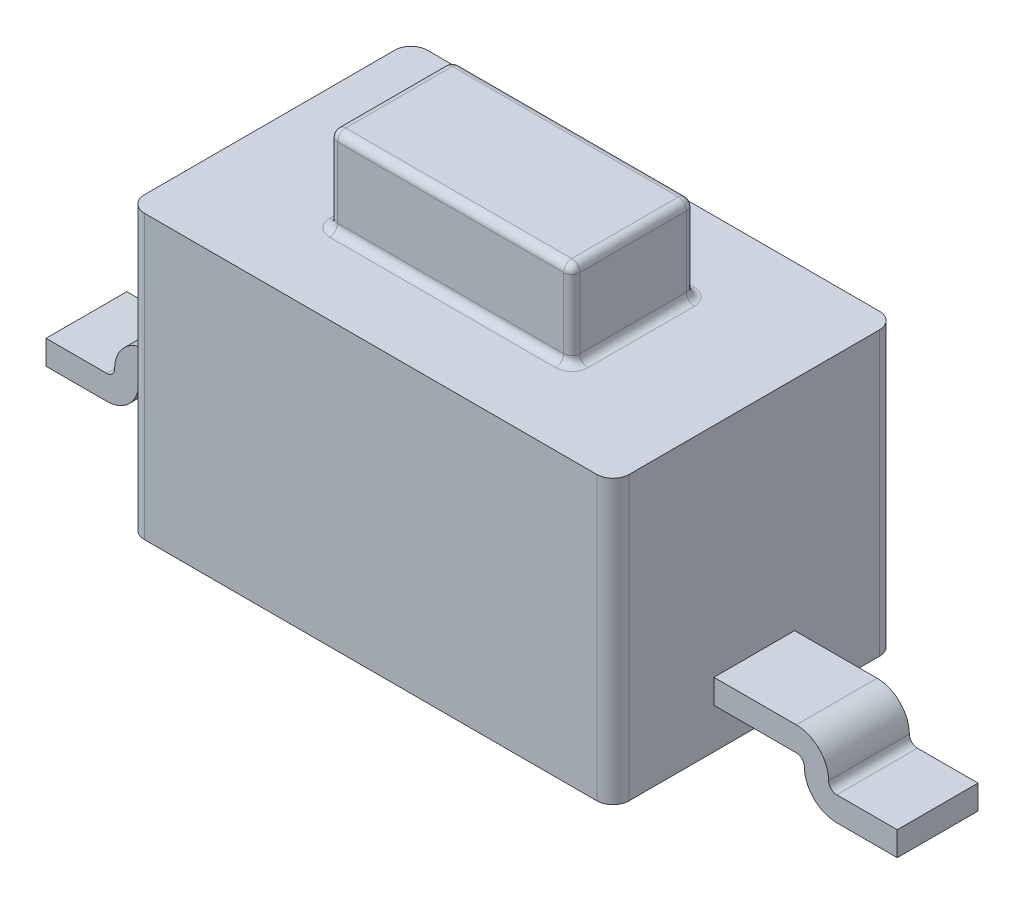
SolidWorks part; units mm, degrees
ref_plane "Front Plane" through (0, 0, 0) normal (0, 0, 1) x (1, 0, 0)
ref_plane "Top Plane" through (0, 0, 0) normal (0, 1, 0) x (1, 0, 0)
ref_plane "Right Plane" through (0, 0, 0) normal (1, 0, 0) x (0, 0, -1)
sketch "Sketch1" plane through (0, 0, 0) normal (0, 1, 0) x (1, 0, 0)
  line L0 (0, 4.6661) -> (0, -3.6864) construction
  line L1 (-7.6307, 0) -> (8.9196, 0) construction
  line L3 (-3, 1.75) -> (3, 1.75)
  line L4 (-3, 1.75) -> (-3, -1.75)
  line L5 (-3, -1.75) -> (3, -1.75)
  line L6 (3, 1.75) -> (3, -1.75)
  dimension "D1" = 3.5
  dimension "D2" = 6
  dimension "D3" = 3
  dimension "D4" = 1.75
extrude "Boss-Extrude1" add sketch "Sketch1" along normal blind 3.5
fillet "Fillet1" radius 0.2 4 edges at (-3, 1.75, -1.75) (3, 1.75, -1.75) (3, 1.75, 1.75) (-3, 1.75, 1.75)
sketch "Sketch2" plane through (0, 3.5, 0) normal (0, 1, 0) x (1, 0, 0)
  line L0 (0, 1.6315) -> (0, -1.6435) construction
  line L1 (-2.8003, 0) -> (2.578, 0) construction
  line L3 (-1.5, -0.76) -> (1.5, -0.76)
  line L4 (-1.5, -0.76) -> (-1.5, 0.76)
  line L5 (-1.5, 0.76) -> (1.5, 0.76)
  line L6 (1.5, -0.76) -> (1.5, 0.76)
  line L7 (-1.5, -0.76) -> (1.5, 0.76) construction
  line L8 (-1.5, 0.76) -> (1.5, -0.76) construction
  point P5 (0, 0)
  dimension "D1" = 3
  dimension "D2" = 1.52
extrude "Boss-Extrude2" add sketch "Sketch2" along normal blind 1.07
fillet "Fillet2" radius 0.1 12 edges at (1.5, 3.5, 0) (1.5, 4.035, -0.76) (0, 3.5, -0.76) (-1.5, 4.035, -0.76) (-1.5, 3.5, 0) (-1.5, 4.035, 0.76) (1.5, 4.035, 0.76) (0, 3.5, 0.76) (0, 4.57, 0.76) (-1.5, 4.57, 0) (0, 4.57, -0.76) (1.5, 4.57, 0)
sketch "Sketch3" plane through (3, 0, 0) normal (1, 0, 0) x (0, 0, -1)
  line L0 (0, 0) -> (0, 2.9277) construction
  line L2 (-0.5, 0.5) -> (0.5, 0.5)
  line L3 (-0.5, 0.5) -> (-0.5, 0.8)
  line L4 (-0.5, 0.8) -> (0.5, 0.8)
  line L5 (0.5, 0.5) -> (0.5, 0.8)
  line L6 (-0.5, 0.5) -> (0.5, 0.8) construction
  line L7 (-0.5, 0.8) -> (0.5, 0.5) construction
  point P3 (0, 0.65)
  dimension "D1" = 0.65
  dimension "D2" = 1
  dimension "D3" = 0.3
sketch "Sketch4" plane through (0, 0, 0) normal (0, 0, 1) x (1, 0, 0)
  line L0 (3, 0.65) -> (4.02, 0.65)
  line L1 (4.02, 0.65) -> (4.02, 0.4) construction
  line L2 (4.27, 0.4) -> (4.52, 0.4) construction
  line L3 (4.52, 0.15) -> (5.27, 0.15)
  arc A0 (4.02, 0.65) -> (4.27, 0.4) centre (4.02, 0.4) cw
  arc A1 (4.27, 0.4) -> (4.52, 0.15) centre (4.52, 0.4) ccw
  dimension "D1" = 1.02
  dimension "D2" = 0.25
  dimension "D3" = 0.25
  dimension "D4" = 0.75
sweep "Sweep1" add profiles "Sketch3" path "Sketch4"
ref_axis "Axis1" through (0, 4.7985, 0) along (0, -1, 0)
pattern_circular "CirPattern1" count 2 every 180 about axis through (0, 4.7985, 0) along (0, -1, 0) of "Sweep1"
